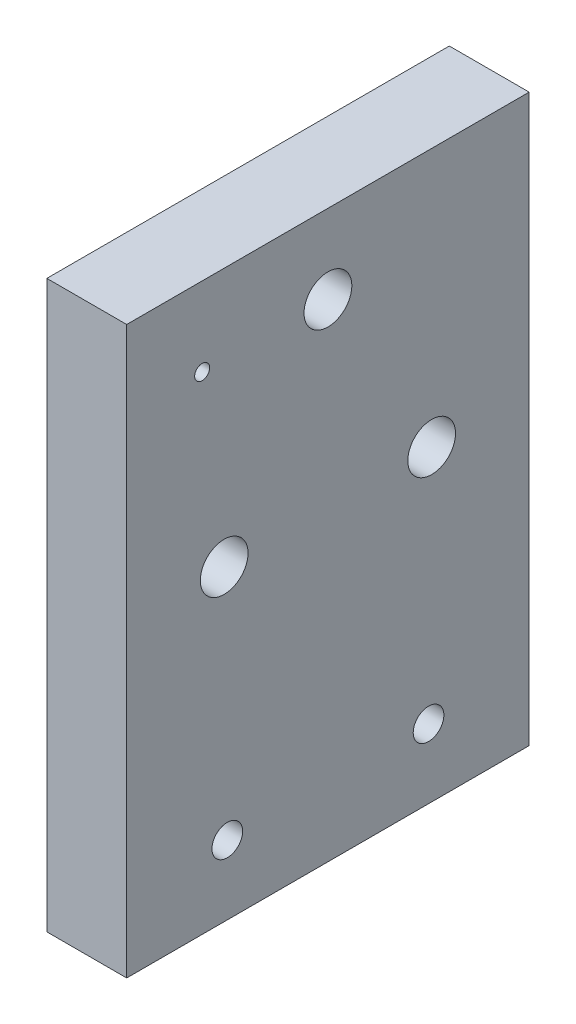
SolidWorks part; units mm, degrees
material "6061-T4 (SS)"
ref_plane "Front Plane" through (0, 0, 0) normal (0, 0, 1) x (1, 0, 0)
ref_plane "Top Plane" through (0, 0, 0) normal (0, 1, 0) x (1, 0, 0)
ref_plane "Right Plane" through (0, 0, 0) normal (1, 0, 0) x (0, 0, -1)
sketch "Sketch1" plane through (0, 0, 0) normal (0, 1, 0) x (1, 0, 0)
  line L1 (-36.5, 16) -> (36.5, 16)
  line L2 (-36.5, 16) -> (-36.5, -16)
  line L3 (-36.5, -16) -> (36.5, -16)
  line L4 (36.5, 16) -> (36.5, -16)
  line L5 (-36.5, 16) -> (36.5, -16) construction
  line L6 (-36.5, -16) -> (36.5, 16) construction
  point P0 (0, 0)
  dimension "D1" = 73
  dimension "D2" = 32
sketch "Sketch26" plane through (0, 0, 0) normal (0, 1, 0) x (-1, 0, 0)
  line L1 (-6.35, 0) -> (0, 0)
  line L2 (-6.35, 0) -> (-6.35, 32)
  line L3 (-6.35, 32) -> (0, 32)
  line L4 (0, 0) -> (0, 32)
  dimension "D1" = 6.35
  dimension "D2" = 32
extrude "Boss-Extrude2" add sketch "Sketch26" along normal blind 45
sketch "Sketch27" plane through (0, 0, 0) normal (-1, 0, 0) x (0, 0, 1)
  line L0 (32, 45) -> (0, 45) construction
  line L1 (0, 45) -> (0, 0) construction
  line L3 (7.7511, 24.4375) -> (24.2489, 24.4375) construction
  line L4 (16, 24.4375) -> (16, 38.725) construction
  line L5 (7.7511, 24.4375) -> (32, 24.4375) construction
  line L7 (24.2489, 24.4375) -> (0, 24.4375) construction
  line L9 (32, 45) -> (32, 0) construction
  circle A0 centre (16, 38.725) radius 1.595
  circle A1 centre (24.2489, 24.4375) radius 1.595
  circle A2 centre (7.7511, 24.4375) radius 1.595
  dimension "D1" = 3.19
  dimension "D2" = 3.19
  dimension "D3" = 3.19
  dimension "D6" = 14.2875
  dimension "D7" = 16.4978
  dimension "D8" = 6.275
extrude "Cut-Extrude7" cut sketch "Sketch27" against normal up to next
hole_wizard "CBORE for #6 Binding Head Machine Screw1" positions "Sketch57" profile "Sketch58" counterbore size "#6" standard "ANSI Inch"
sketch "Sketch57" plane through (0, 0, 0) normal (-1, 0, 0) x (0, 0, 1)
  point P0 (16, 38.725)
  point P3 (24.2489, 24.4375)
  point P6 (7.7511, 24.4375)
sketch "Sketch58" plane through (0, 38.725, 16) normal (0, 1, 0) x (0, 0, 1)
  line L0 (0, 0) -> (0, 47.6408)
  line L1 (0, 47.6408) -> (1.8986, 46.5)
  line L2 (1.8986, 46.5) -> (1.8986, 1.016)
  line L3 (1.8986, 1.016) -> (4.7625, 1.016)
  line L4 (4.7625, 1.016) -> (4.7625, 0)
  line L5 (4.7625, 0) -> (0, 0)
  line L10 (0, 47.6408) -> (-1.8987, 46.5) construction
  line L11 (0, -6.35) -> (0, 107.95) construction
  dimension "Hole Dia." = 3.7973
  dimension "Hole Depth" = 46.5
  dimension "C'Bore Dia." = 9.525
  dimension "C'Bore Depth" = 1.016
  dimension "Drill Angle" = 118
sketch "Sketch88" plane through (0, 0, 0) normal (-1, 0, 0) x (0, 0, 1)
  line L0 (32, 45) -> (32, 0) construction
  point P0 (32, 22.5)
hole_wizard "#0-80 Tapped Hole1" positions "Sketch93" profile "Sketch94" tap size "#0-80" standard "ANSI Inch" end condition through all
sketch "Sketch93" plane through (0, 0, 0) normal (-1, 0, 0) x (0, 0, 1)
  line L4 (16, 38.725) -> (26, 38.725) construction
  line L5 (26, 38.725) -> (0, 38.725) construction
  line L7 (0, 45) -> (0, 0) construction
  line L8 (32, 45) -> (0, 45) construction
  circle A0 centre (16, 38.725) radius 4.7625 construction
  point P0 (26, 38.725)
  dimension "D1" = 10
  dimension "D2" = 6.275
sketch "Sketch94" plane through (0, 38.725, 26) normal (0, 1, 0) x (0, 0, 1)
  line L0 (0, 0) -> (0, 6.35)
  line L1 (0, 6.35) -> (0.5956, 6.35)
  line L2 (0.5956, 6.35) -> (0.5956, 0)
  line L5 (0.5956, 0) -> (0, 0)
  line L11 (0, -6.35) -> (0, 107.95) construction
  dimension "Thread Major Dia." = 1.1913
  dimension "Thru Tap Drill Depth" = 6.35
hole_wizard "#2 Clearance Hole1" positions "Sketch101" profile "Sketch102" hole size "#2" standard "ANSI Inch"
sketch "Sketch101" plane through (0, 0, 0) normal (-1, 0, 0) x (0, 0, 1)
  point P0 (8, 5.5)
  point P3 (24, 5.5)
sketch "Sketch102" plane through (0, 5.5, 8) normal (0, 1, 0) x (0, 0, 1)
  line L0 (0, 0) -> (0, 21.0526)
  line L1 (0, 21.0526) -> (1.2192, 20.32)
  line L2 (1.2192, 20.32) -> (1.2192, 0)
  line L5 (1.2192, 0) -> (0, 0)
  line L10 (0, 21.0526) -> (-1.2192, 20.32) construction
  line L11 (0, -6.35) -> (0, 107.95) construction
  dimension "Hole Dia." = 2.4384
  dimension "Hole Depth" = 20.32
  dimension "Drill Angle" = 118
